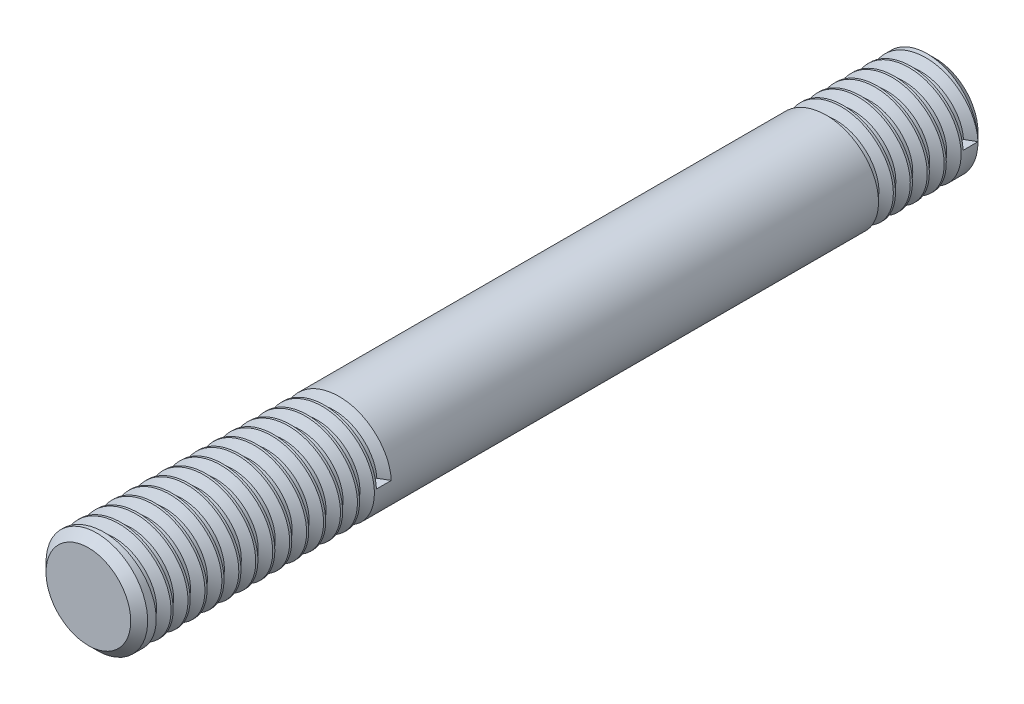
SolidWorks part; units mm, degrees
material "Plain Carbon Steel"
ref_plane "Front Plane" through (0, 0, 0) normal (0, 0, 1) x (1, 0, 0)
ref_plane "Top Plane" through (0, 0, 0) normal (0, 1, 0) x (1, 0, 0)
ref_plane "Right Plane" through (0, 0, 0) normal (1, 0, 0) x (0, 0, -1)
sketch "Sketch1" plane through (0, 0, 0) normal (0, 0, 1) x (1, 0, 0)
  circle A0 centre (0, 0) radius 1.5
  dimension "D1" = 3
extrude "Boss-Extrude1" add sketch "Sketch1" along normal blind 25
chamfer "Chamfer2" distance 0.25 angle 45 2 edges at (1.5, 0, 25) (1.5, 0, 0)
thread "Thread3" pitch 0.5 method cut profile "Thread Profile4" start angle 0, offset 0, length 2.75, pitch 0.5, diameter 3
ref_plane "Plane4" through (1.5, 0, 0.25) normal (0, -1, 0) x (1, 0, 0)
sketch "Thread Profile4" plane through (1.5, 0, 0.25) normal (0, -1, 0) x (1, 0, 0)
  line L0 (0, 0) -> (0, 0.5) construction
  line L11 (0, 0) -> (0, 0.4375)
  line L12 (0, 0.4375) -> (-0.2706, 0.2812)
  line L13 (-0.2706, 0.2812) -> (-0.2706, 0.1562)
  line L15 (-0.2706, 0.1562) -> (0, 0)
  line L17 (-0.2706, 0.2187) -> (0, 0.2187) construction
  point P2 (0, 0)
  dimension "Pitch" = 0.5
  dimension "Profile_Angle" = 60
  dimension "Profile_Land" = 0.125
  dimension "Profile_Height" = 0.2706
thread "Thread4" pitch 0.5 method cut profile "Thread Profile5" start angle 0, offset 0, length 6.75, pitch 0.5, diameter 3
ref_plane "Plane5" through (-1.5, 0, 24.75) normal (0, -1, 0) x (-1, 0, 0)
sketch "Thread Profile5" plane through (-1.5, 0, 24.75) normal (0, -1, 0) x (-1, 0, 0)
  line L0 (0, 0) -> (0, 0.5) construction
  line L11 (0, 0) -> (0, 0.4375)
  line L12 (0, 0.4375) -> (-0.2706, 0.2812)
  line L13 (-0.2706, 0.2812) -> (-0.2706, 0.1562)
  line L15 (-0.2706, 0.1562) -> (0, 0)
  line L17 (-0.2706, 0.2187) -> (0, 0.2187) construction
  point P2 (0, 0)
  dimension "Pitch" = 0.5
  dimension "Profile_Angle" = 60
  dimension "Profile_Land" = 0.125
  dimension "Profile_Height" = 0.2706
